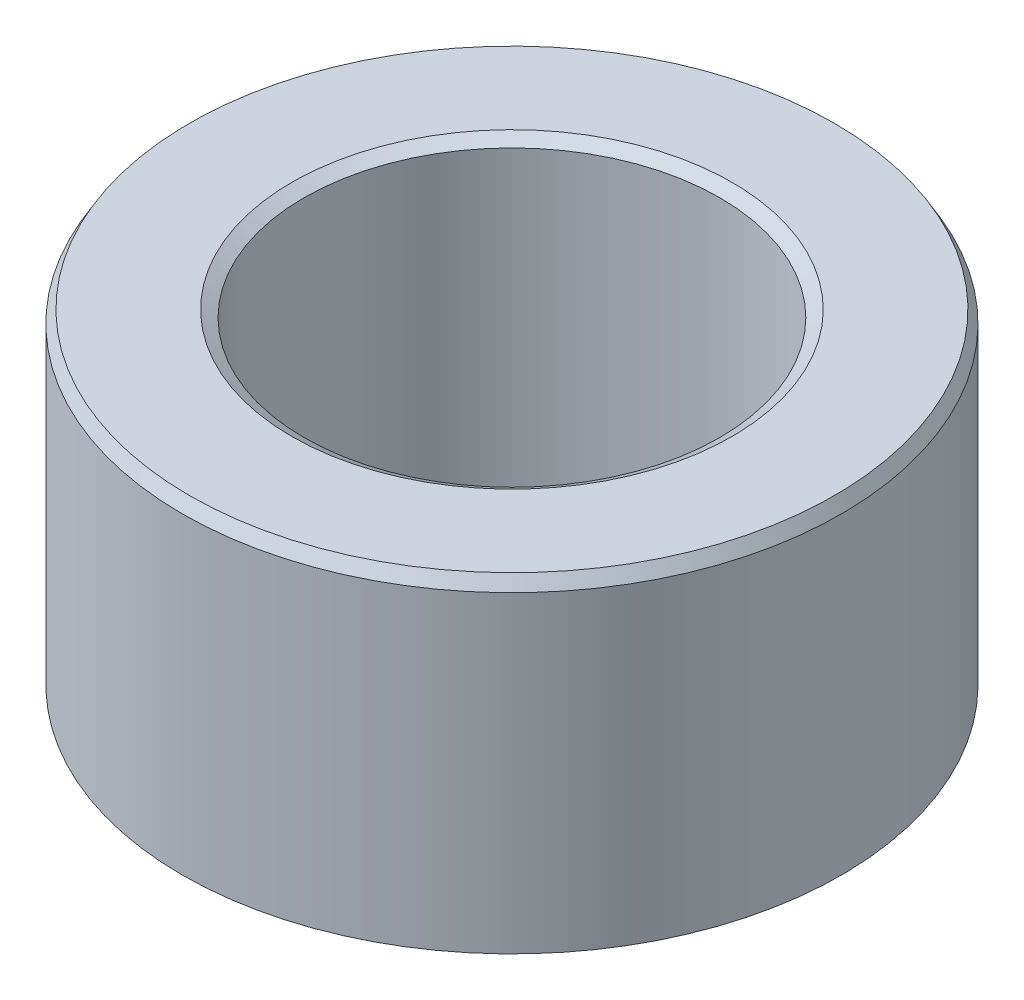
SolidWorks part; units mm, degrees
ref_plane "Front Plane" through (0, 0, 0) normal (0, 0, 1) x (1, 0, 0)
ref_plane "Top Plane" through (0, 0, 0) normal (0, 1, 0) x (1, 0, 0)
ref_plane "Right Plane" through (0, 0, 0) normal (1, 0, 0) x (0, 0, -1)
sketch "Sketch1" plane through (0, 0, 0) normal (0, 1, 0) x (1, 0, 0)
  circle A0 centre (0, 0) radius 45
  dimension "SLEEVE_OD" = 90
extrude "Boss-Extrude1" add sketch "Sketch1" along normal blind 45.3636
sketch "Sketch2" plane through (0, 0, 0) normal (0, 1, 0) x (1, 0, 0)
  circle A0 centre (0, 0) radius 28.3773
  dimension "BORE_D" = 56.7546
extrude "Cut-Extrude1" cut sketch "Sketch2" along normal through all
chamfer "Chamfer1" distance 1.6814 angle 30 4 edges at (0, 45.3636, 28.3773) (0, 0, 28.3773) (0, 0, 45) (0, 45.3636, 45) first distance on face at (0, 45.3636, 28.3773) first distance on face at (0, 0, 28.3773) first distance on face at (0, 45.3636, 45)
